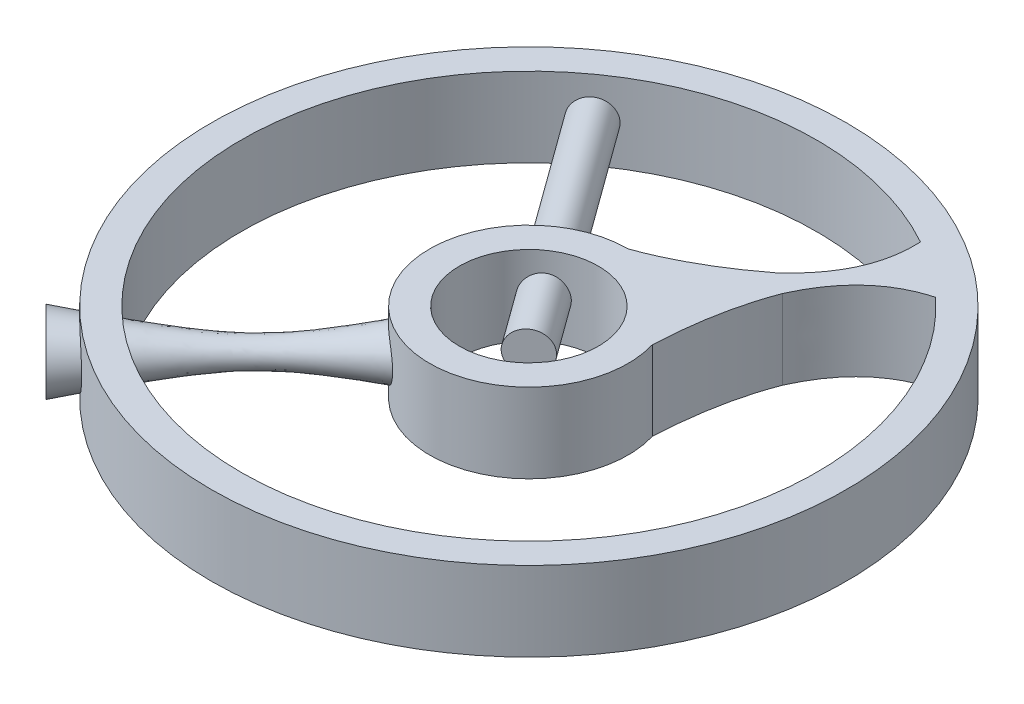
SolidWorks part; units mm, degrees
ref_plane "Front Plane" through (0, 0, 0) normal (0, 0, 1) x (1, 0, 0)
ref_plane "Top Plane" through (0, 0, 0) normal (0, 1, 0) x (1, 0, 0)
ref_plane "Right Plane" through (0, 0, 0) normal (1, 0, 0) x (0, 0, -1)
sketch "Sketch2" plane through (0, 0, 0) normal (0, 1, 0) x (1, 0, 0)
  circle A0 centre (0, 0) radius 160
  circle A1 centre (0, 0) radius 145
extrude "Outer Ring" add sketch "Sketch2" along normal blind 40
sketch "Sketch3" plane through (0, 0, 0) normal (0, 1, 0) x (1, 0, 0)
  circle A0 centre (0, 0) radius 50
  circle A1 centre (0, 0) radius 35
extrude "Inner" add sketch "Sketch3" along normal blind 40 separate body
sketch "Sketch4" plane through (0, 0, 0) normal (0, 1, 0) x (1, 0, 0)
  line L0 (0, 0) -> (85.2289, 117.3075) construction
  line L1 (0, 0) -> (145, 0) construction
  line L2 (0, 0) -> (0, 145) construction
  line L3 (0, 50) -> (70.6402, 120.7117) construction
  line L4 (47.9169, 14.2819) -> (92.9746, 104.4848) construction
  line L5 (35.3201, 85.3559) -> (70.4458, 59.3834) construction
  arc A0 (0, 50) -> (47.9169, 14.2819) centre (0, 0) cw
  circle A1 centre (0, 0) radius 145 construction
  arc A2 (70.6402, 126.6292) -> (98.6025, 106.3134) centre (0, 0) cw
  circle A3 centre (0, 0) radius 50 construction
  spline S0 degree 3 poles (0, 50) (15.5027, 55.3917) (32.3208, 64.9165) (47.9169, 76.9392) knots 0 0 0 0 0.490217 0.490217 0.490217 0.490217
  spline S1 degree 3 poles (47.9169, 14.2819) (48.6558, 30.6788) (51.2995, 50.9667) (58.3664, 69.3472) knots 0 0 0 0 0.490217 0.490217 0.490217 0.490217
  spline S2 degree 2 poles (47.9169, 76.9392) (72.0035, 98.6781) (70.6402, 126.6292) knots 0 0 0 1 1 1
  spline S3 degree 2 poles (58.3664, 69.3472) (71.5982, 98.9726) (98.6025, 106.3134) knots 0 0 0 1 1 1
  dimension "D1" = 145
extrude "Strut [Extruded Form]" add sketch "Sketch4" along normal blind 40
ref_plane "Plane1" through (0, 20, 0) normal (0, 1, 0) x (1, 0, 0)
sketch "Sketch8" plane through (0, 20, 0) normal (0, 1, 0) x (1, 0, 0)
  line L0 (0, 0) -> (0, 145) construction
  line L1 (0, 0) -> (-145, 0) construction
  line L2 (0, 0) -> (-85.2289, 117.3075) construction
  line L3 (-85.2289, 117.3075) -> (0, 0)
  arc A0 (70.6402, 126.6292) -> (98.6025, 106.3134) centre (0, 0) ccw construction
  point P7 (0, 0)
  point P10 (0, 0)
revolve "Revolve-Thin3" add sketch "Sketch8" angle 360 mid plane about L2 wall 10
ref_plane "Plane2" through (0, 0, 0) normal (-0.7071, 0, 0.7071) x (0.7071, 0, 0.7071)
ref_plane "Plane3" through (-30.4056, 0, 30.4056) normal (-0.7071, 0, 0.7071) x (0.7071, 0, 0.7071)
ref_plane "Plane4" through (-60.8112, 0, 60.8112) normal (-0.7071, 0, 0.7071) x (0.7071, 0, 0.7071)
ref_plane "Plane5" through (-91.2168, 0, 91.2168) normal (-0.7071, 0, 0.7071) x (0.7071, 0, 0.7071)
ref_plane "Plane6" through (-121.6224, 0, 121.6224) normal (-0.7071, 0, 0.7071) x (0.7071, 0, 0.7071)
sketch "Sketch10" plane through (0, 0, 0) normal (-0.7071, 0, 0.7071) x (0.7071, 0, 0.7071)
  line L0 (176, 20) -> (-176, 20) construction
  circle A0 centre (0, 20) radius 13
sketch "Sketch11" plane through (-30.4056, 0, 30.4056) normal (-0.7071, 0, 0.7071) x (0.7071, 0, 0.7071)
  circle A0 centre (0, 20) radius 13
sketch "Sketch12" plane through (-60.8112, 0, 60.8112) normal (-0.7071, 0, 0.7071) x (0.7071, 0, 0.7071)
  circle A0 centre (0, 20) radius 7
sketch "Sketch14" plane through (-121.6224, 0, 121.6224) normal (-0.7071, 0, 0.7071) x (0.7071, 0, 0.7071)
  circle A0 centre (0, 20.0857) radius 17
loft "Loft1" add profiles "Sketch14", "Sketch11" connector at (-133.6266, 20.9772, 109.6181) connector at (-24.7578, 30.257, 36.0534)
